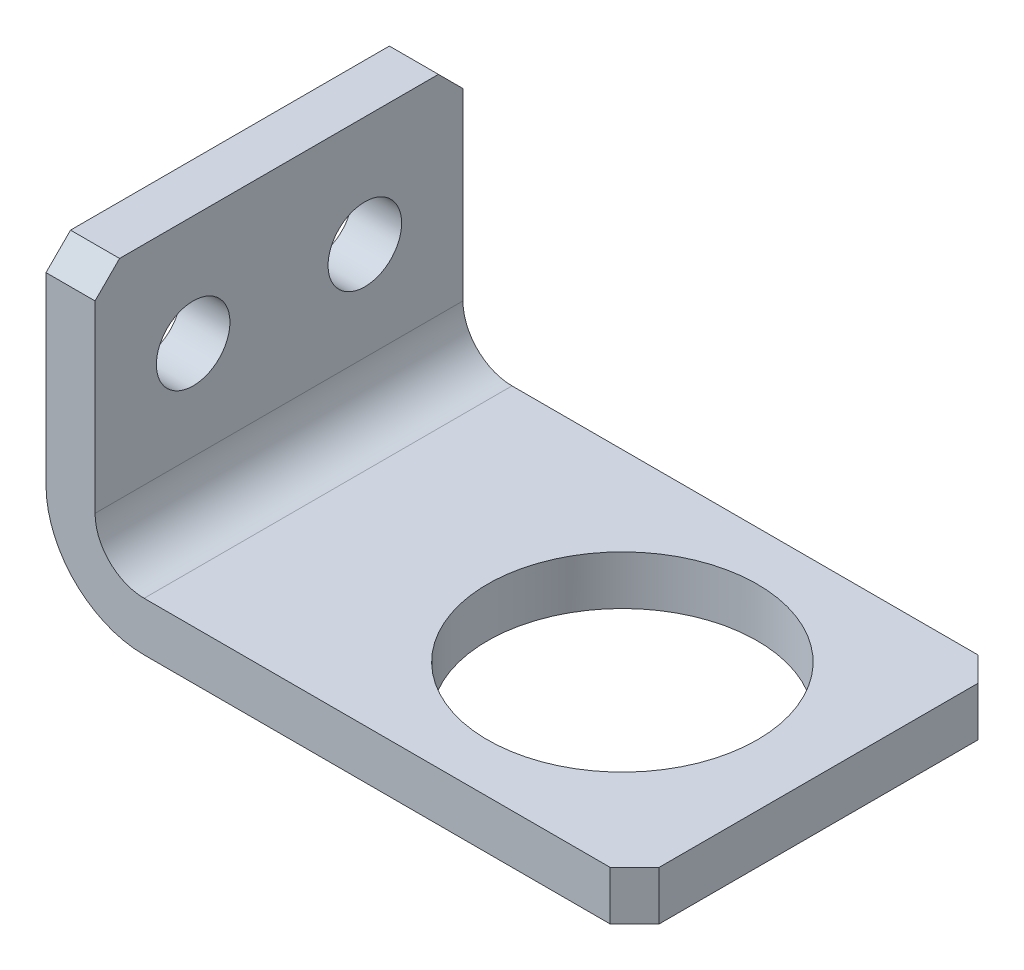
SolidWorks part; units mm, degrees
ref_plane "前视基准面" through (0, 0, 0) normal (0, 0, 1) x (1, 0, 0)
ref_plane "上视基准面" through (0, 0, 0) normal (0, 1, 0) x (1, 0, 0)
ref_plane "右视基准面" through (0, 0, 0) normal (1, 0, 0) x (0, 0, -1)
sketch "草图1" plane through (0, 0, 0) normal (0, 1, 0) x (1, 0, 0)
  line L1 (24, -15) -> (-24, -15)
  line L2 (24, -15) -> (24, 15)
  line L3 (24, 15) -> (-24, 15)
  line L4 (-24, -15) -> (-24, 15)
  line L5 (24, -15) -> (-24, 15) construction
  line L6 (24, 15) -> (-24, -15) construction
  point P0 (0, 0)
  dimension "D1" = 30
  dimension "D2" = 48
extrude "凸台-拉伸1" add sketch "草图1" along normal blind 25
sketch "草图2" plane through (0, 0, 15) normal (0, 0, 1) x (1, 0, 0)
  line L0 (-24, 8) -> (-24, 25)
  line L1 (-24, 0) -> (24, 0) construction
  line L2 (24, 4) -> (24, 0)
  line L3 (-24, 25) -> (-24, 0) construction
  line L4 (-20, 8) -> (-20, 25)
  line L5 (-24, 25) -> (24, 25) construction
  line L6 (-16, 4) -> (24, 4)
  line L7 (24, 25) -> (24, 0) construction
  line L8 (-24, 25) -> (-20, 25)
  line L9 (-20, 25) -> (24, 25)
  line L10 (24, 4) -> (24, 25)
  line L11 (-24, 8) -> (-24, 0)
  line L12 (24, 0) -> (-16, 0)
  line L13 (-24, 0) -> (-16, 0)
  arc A0 (-24, 8) -> (-16, 0) centre (-16, 8) ccw
  arc A1 (-20, 8) -> (-16, 4) centre (-16, 8) ccw
  line M5 (-24, 0) -> (24, 0)
  line M6 (24, 0) -> (24, 25)
  line M7 (24, 25) -> (-24, 25)
  line M8 (-24, 25) -> (-24, 0)
extrude "切除-拉伸1" cut sketch "草图2" against normal through all contours L4 A1 L6 M6 M7 | A0 M8 M5 region at (-22.2131, 1.7869, 15) region at (2.0787, 14.5358, 15)
sketch "草图4" plane through (0, 0, 0) normal (1, 0, 0) x (0, 0, -1)
  line L0 (0, 25) -> (0, 0) construction
  line L1 (15, 25) -> (-15, 25) construction
  line L2 (-7, 25) -> (-7, 8.1721)
  line L3 (0, 16) -> (-9.7545, 16)
  circle A0 centre (-7, 16) radius 3
  circle A1 centre (7, 16) radius 3
  dimension "D1" = 7
  dimension "D2" = 9
extrude "切除-拉伸2" cut sketch "草图4" against normal through all contours A1 | A0
sketch "草图5" plane through (0, 0, 0) normal (0, 1, 0) x (1, 0, 0)
  line L0 (8, 15) -> (8, -15)
  line L1 (-16, 15) -> (24, 15) construction
  line L2 (-16, -15) -> (24, -15) construction
  line L3 (24, 15) -> (24, -15) construction
  circle A0 centre (8, 0) radius 11
  dimension "D1" = 16
extrude "切除-拉伸4" cut sketch "草图5" along normal through all contours A0
fillet "倒角2" radius 2 1 edges at (24, 2, -15) type face fillet profile chamfer first side face at (24, 2, 0) second side face at (-9.3107, 8.9393, -15)
fillet "倒角3" radius 2 1 edges at (24, 2, 15) type face fillet profile chamfer first side face at (24, 2, 1) second side face at (-9.3107, 8.9393, 15)
fillet "倒角4" radius 2 1 edges at (-22, 25, -15) type face fillet profile chamfer first side face at (-22, 25, 0) second side face at (-9.8107, 8.9393, -15)
fillet "倒角5" radius 2 1 edges at (-22, 25, 15) type face fillet profile chamfer first side face at (-22, 25, 1) second side face at (-9.8107, 8.9393, 15)
